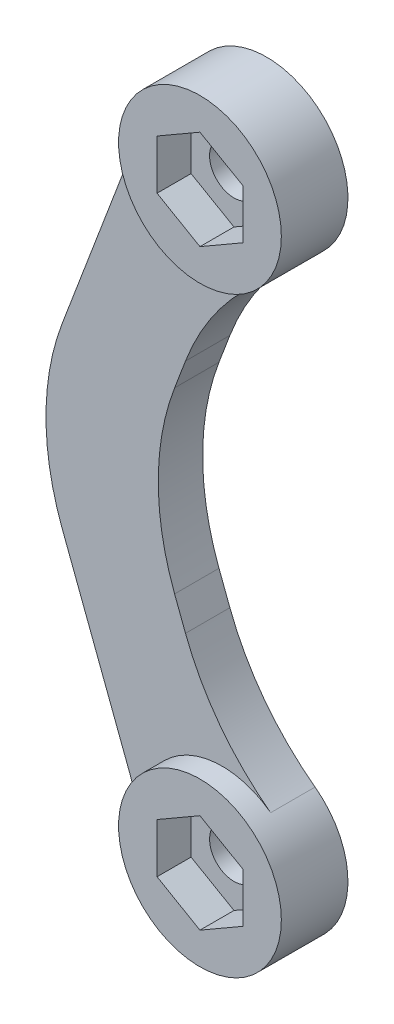
SolidWorks part; units mm, degrees
ref_plane "Front Plane" through (0, 0, 0) normal (0, 0, 1) x (1, 0, 0)
ref_plane "Top Plane" through (0, 0, 0) normal (0, 1, 0) x (1, 0, 0)
ref_plane "Right Plane" through (0, 0, 0) normal (1, 0, 0) x (0, 0, -1)
sketch "草图1" plane through (0, 0, 0) normal (0, 0, 1) x (1, 0, 0)
  line L0 (-26.8116, -1.2161) -> (16.1865, -1.2161) construction
  line L14 (-5.0877, -1.2161) -> (0.4123, -15.7161)
  line L16 (-5.0877, -21.2161) -> (-12.674, -1.2161)
  line L18 (-5.0877, -21.2161) -> (-5.0877, 3.4369) construction
  line L19 (-5.0877, 18.7839) -> (-12.674, -1.2161)
  line L20 (-5.0877, -1.2161) -> (0.4123, 13.2839)
  arc A0 (0.4123, -15.7161) -> (-5.0877, -21.2161) centre (0.4123, -21.2161) cw
  circle A5 centre (0.4123, -21.2161) radius 1.65
  circle A6 centre (0.4123, 18.7839) radius 1.65
  arc A7 (0.4123, 13.2839) -> (-5.0877, 18.7839) centre (0.4123, 18.7839) ccw
  point P0 (-12.6689, -1.2161)
  dimension "D5" = 3.3
  dimension "D6" = 5.5
  dimension "D1" = 20
extrude "凸台-拉伸1" add sketch "草图1" along normal blind 3
sketch "草图2" plane through (0, 0, 3) normal (0, 0, 1) x (1, 0, 0)
  line L0 (-2.4877, 20.4582) -> (-2.4877, 17.1096)
  line L1 (3.3123, 20.4582) -> (3.3123, 17.1096)
  line L2 (-2.4877, 20.4582) -> (0.4123, 22.1326)
  line L3 (0.4123, 22.1326) -> (3.3123, 20.4582)
  line L4 (-2.4877, 17.1096) -> (0.4123, 15.4353)
  line L5 (0.4123, 15.4353) -> (3.3123, 17.1096)
  line L6 (0.4123, 22.1326) -> (0.4123, 15.4353) construction
  line L7 (-2.4877, 17.1096) -> (3.3123, 20.4582) construction
  line L8 (-2.4877, -19.5418) -> (-2.4877, -22.8904)
  line L9 (3.3123, -19.5418) -> (3.3123, -22.8904)
  line L10 (-2.4877, -19.5418) -> (0.4123, -17.8674)
  line L11 (0.4123, -17.8674) -> (3.3123, -19.5418)
  line L12 (-2.4877, -22.8904) -> (0.4123, -24.5647)
  line L13 (0.4123, -24.5647) -> (3.3123, -22.8904)
  line L14 (0.4123, -17.8674) -> (0.4123, -24.5647) construction
  line L15 (-2.4877, -22.8904) -> (3.3123, -19.5418) construction
  circle A0 centre (0.4123, 18.7839) radius 5.5
  circle A1 centre (0.4123, -21.2161) radius 5.5
  arc A2 (-5.0877, -21.2161) -> (0.4123, -15.7161) centre (0.4123, -21.2161) ccw construction
  point P4 (0.4123, 18.7839)
  point P11 (0.4123, -21.2161)
  point P24 (0, 0)
  point P25 (14.6523, 16.8296)
  point P26 (0, 0)
  point P27 (0.4123, 18.7839)
  dimension "D1" = 5.8
  dimension "D2" = 60
  dimension "D3" = 120
  dimension "D4" = 120
  dimension "D5" = 5.8
extrude "凸台-拉伸2" add sketch "草图2" along normal blind 1.5
sketch "草图3" plane through (0, 0, 3) normal (0, 0, 1) x (1, 0, 0)
  line L0 (0.4123, 22.1326) -> (-2.4877, 20.4582)
  line L1 (-2.4877, 20.4582) -> (-2.4877, 17.1096)
  line L2 (-2.4877, 17.1096) -> (0.4123, 15.4353)
  line L3 (0.4123, 15.4353) -> (3.3123, 17.1096)
  line L4 (3.3123, 17.1096) -> (3.3123, 20.4582)
  line L5 (3.3123, 20.4582) -> (0.4123, 22.1326)
  line L6 (0.4123, -17.8674) -> (-2.4877, -19.5418)
  line L7 (-2.4877, -19.5418) -> (-2.4877, -22.8904)
  line L8 (-2.4877, -22.8904) -> (0.4123, -24.5647)
  line L9 (0.4123, -24.5647) -> (3.3123, -22.8904)
  line L10 (3.3123, -22.8904) -> (3.3123, -19.5418)
  line L11 (3.3123, -19.5418) -> (0.4123, -17.8674)
extrude "切除-拉伸1" cut sketch "草图3" against normal blind 0.8
fillet "圆角1" radius 17 6 edges at (-5.0877, 18.7839, 1.5) (-5.0877, -21.2161, 1.5) (0.4123, -15.7161, 1.5) (0.4123, 13.2839, 1.5) (-5.0877, -1.2161, 1.5) (-12.674, -1.2161, 1.5)
